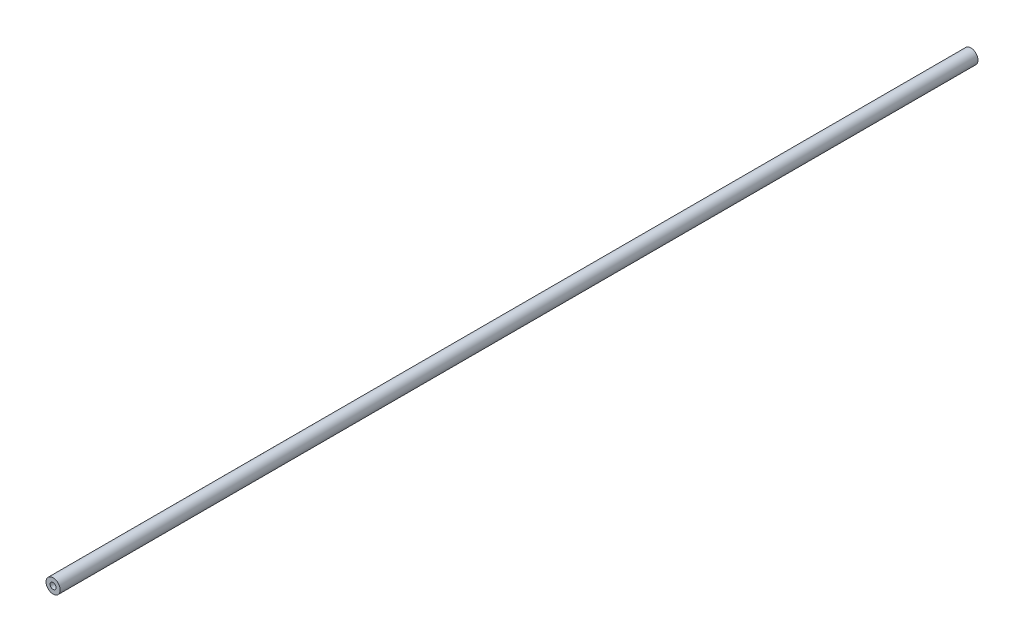
SolidWorks part; units mm, degrees
material "6061-T6 (SS)"
ref_plane "Front Plane" through (0, 0, 0) normal (0, 0, 1) x (1, 0, 0)
ref_plane "Top Plane" through (0, 0, 0) normal (0, 1, 0) x (1, 0, 0)
ref_plane "Right Plane" through (0, 0, 0) normal (1, 0, 0) x (0, 0, -1)
sketch "Sketch1" plane through (0, 0, 0) normal (0, 0, 1) x (1, 0, 0)
  circle A1 centre (0, 0) radius 4.7625
  dimension "D2" = 9.525
extrude "Boss-Extrude1" add sketch "Sketch1" along normal mid plane 615.95
hole_wizard "#10-32 Tapped Hole1" positions "3DSketch1" profile "Sketch2" tap size "#10-32" standard "ANSI Inch"
sketch3d "3DSketch1"
  line L0 (0, 0, 307.975) -> (0, 0, -307.975) construction
  point P0 (0, 0, -307.975)
  point P4 (0, 0, 307.975)
sketch "Sketch2" plane through (0, 0, -307.975) normal (1, 0, 0) x (0, 1, 0)
  line L0 (0, 0) -> (0, 13.2428)
  line L1 (0, 13.2428) -> (2.0193, 12.0294)
  line L2 (2.0193, 12.0294) -> (2.0193, 0)
  line L5 (2.0193, 0) -> (0, 0)
  line L10 (0, 13.2428) -> (-2.0193, 12.0294) construction
  line L11 (0, -6.35) -> (0, 107.95) construction
  dimension "Tap Drill Dia." = 4.0386
  dimension "Tap Drill Depth" = 12.0294
  dimension "Drill Angle" = 118
cosmetic thread "Hole Thread1" parameters "D1"=9.652, "D2"=4.826
cosmetic thread "Hole Thread2" parameters "D1"=9.652, "D2"=4.826
